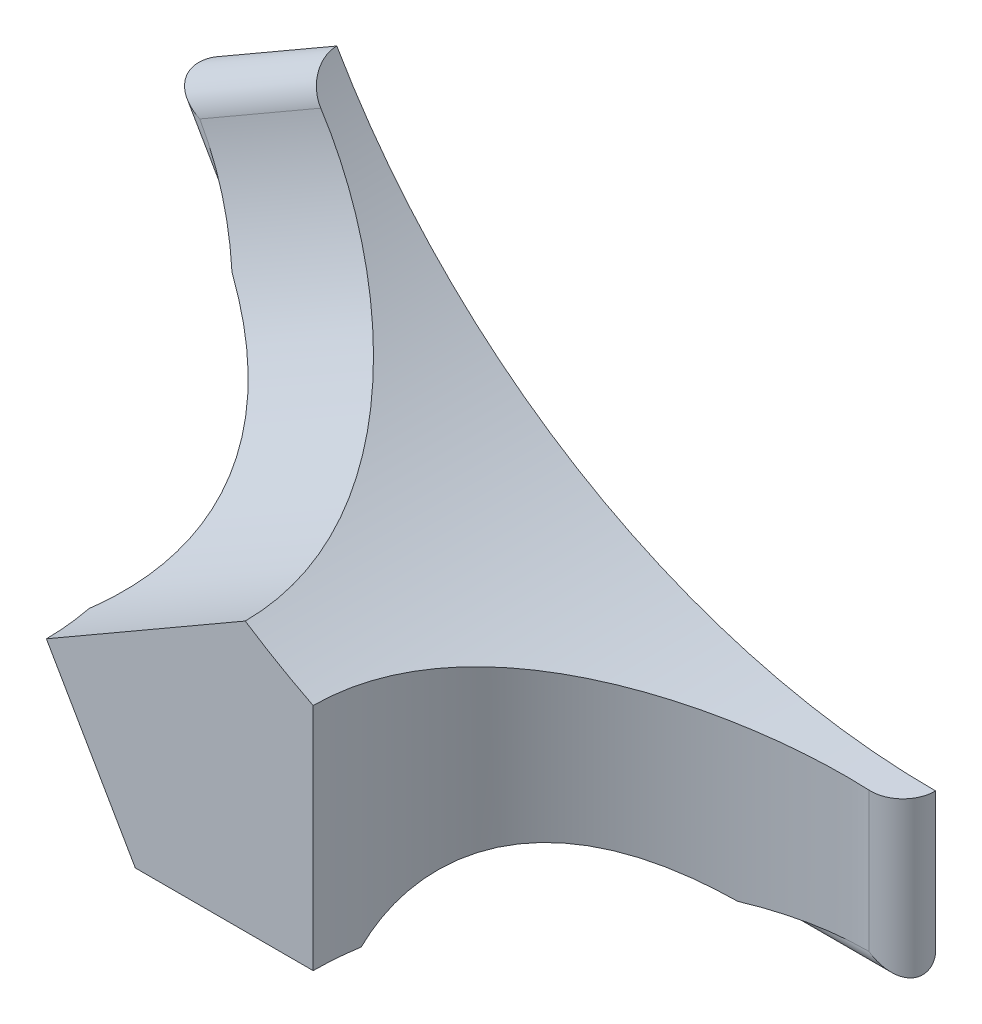
SolidWorks part; units mm, degrees
material "Золото без примесей"
ref_plane "Front" through (0, 0, 0) normal (0, 0, 1) x (1, 0, 0)
ref_plane "Top" through (0, 0, 0) normal (0, 1, 0) x (1, 0, 0)
ref_plane "Right" through (0, 0, 0) normal (1, 0, 0) x (0, 0, -1)
sketch "Эскиз1" plane through (0, 0, 0) normal (0, 0, 1) x (1, 0, 0)
  line L0 (0, 0) -> (22, 0)
  line L1 (22, 0) -> (22, 7)
  line L2 (0, 0) -> (14.4094, 24.9578) construction
  line L4 (6.4474, 11.1673) -> (0, 0)
  line L5 (22, 7) -> (22.8779, 7) construction
  line L6 (6.4474, 11.1673) -> (1.765, 13.8707) construction
  arc A0 (22, 7) -> (6.4474, 11.1673) centre (22, 38.1051) cw
  dimension "D1" = 60
  dimension "D2" = 7
  dimension "D3" = 22
extrude "Основная форма" add sketch "Эскиз1" along normal blind 14
sketch "Эскиз2" plane through (22, 0, 0) normal (1, 0, 0) x (0, 0, -1)
  line L1 (-14, -1) -> (0, -1)
  line L2 (0, 0.75) -> (0, -1)
  line L5 (-14, 0) -> (0, 0) construction
  line L6 (-14, 0) -> (-14, -1)
  line L8 (-14, 0) -> (-12, 0)
  line L10 (-1.5, 0.75) -> (-2.5, 0.75)
  line L11 (0, 0) -> (0, 7) construction
  line L12 (-10.4143, 2.5) -> (-4.9819, 2.5) construction
  arc A3 (-12, 0) -> (-2.5, 0.75) centre (-6.91, -3.9316) cw
  arc A4 (0, 0.75) -> (-1.5, 0.75) centre (-0.75, 0.75) cw
  dimension "D1" = 2.5
  dimension "D2" = 1
  dimension "D3" = 1.5
  dimension "D5" = 1
  dimension "D7" = 2
extrude "Вырез фигурный, фронт" cut sketch "Эскиз2" against normal through all
sketch "Эскиз3" plane through (0, 0, 0) normal (0, 1, 0) x (1, 0, 0)
  line L4 (22, 0) -> (22, -14)
  line L6 (22, -14) -> (8, -14)
  line L9 (0, -14) -> (22, -14) construction
  line L10 (0.433, -1.5) -> (22, -1.5) construction
  line L11 (20.5, -14) -> (20.5, -1.5) construction
  arc A4 (8, -14) -> (20.5, -1.5) centre (20.5, -14) cw
  arc A5 (20.5, -1.5) -> (22, 0) centre (20.5, 0) ccw
extrude "Вырез фигурный, бок" cut sketch "Эскиз3" along normal through all
sketch "Эскиз5" plane through (0, 0, 0) normal (0, 0, -1) x (-1, 0, 0)
  line L1 (-5.0518, 4.75) -> (-2.7424, 4.75) construction
  line L6 (-6.4474, 11.1673) -> (-0.433, 0.75) construction
  line L7 (-22, 0.75) -> (-0.433, 0.75) construction
  line L8 (-3.0518, 5.2859) -> (0.1683, 7.145) construction
  line L9 (0, 0) -> (-1.4434, 2.5) construction
  line L10 (-5.0518, 4.75) -> (-10.7424, 4.75)
  arc A0 (-3.0518, 5.2859) -> (-5.0518, 4.75) centre (-5.0518, 8.75) cw
  dimension "D2" = 4
  dimension "D1" = 4
  dimension "D3" = 8
extrude "Вырез под финсатор" cut sketch "Эскиз5" against normal blind 3 and the other way through all thin thin type mid plane wall 1.4
mirror "Зеркальное отражение1" about plane through (6.4474, 11.1673, 14) normal (0.866, -0.5, 0) of "Вырез под финсатор", "Вырез фигурный, фронт", "Вырез фигурный, бок", "Основная форма"
chamfer "Фаска1" distance 0.5 angle 45 8 edges at (10.7424, 4.75, 0) (7.8971, 5.45, 0) (3.4018, 5.8921, 0) (7.8971, 4.05, 0) (2.7018, 4.6797, 0) (0.7713, 9.5641, 0) (-0.4412, 8.8641, 0) (-1.2576, 11.6782, 0)
